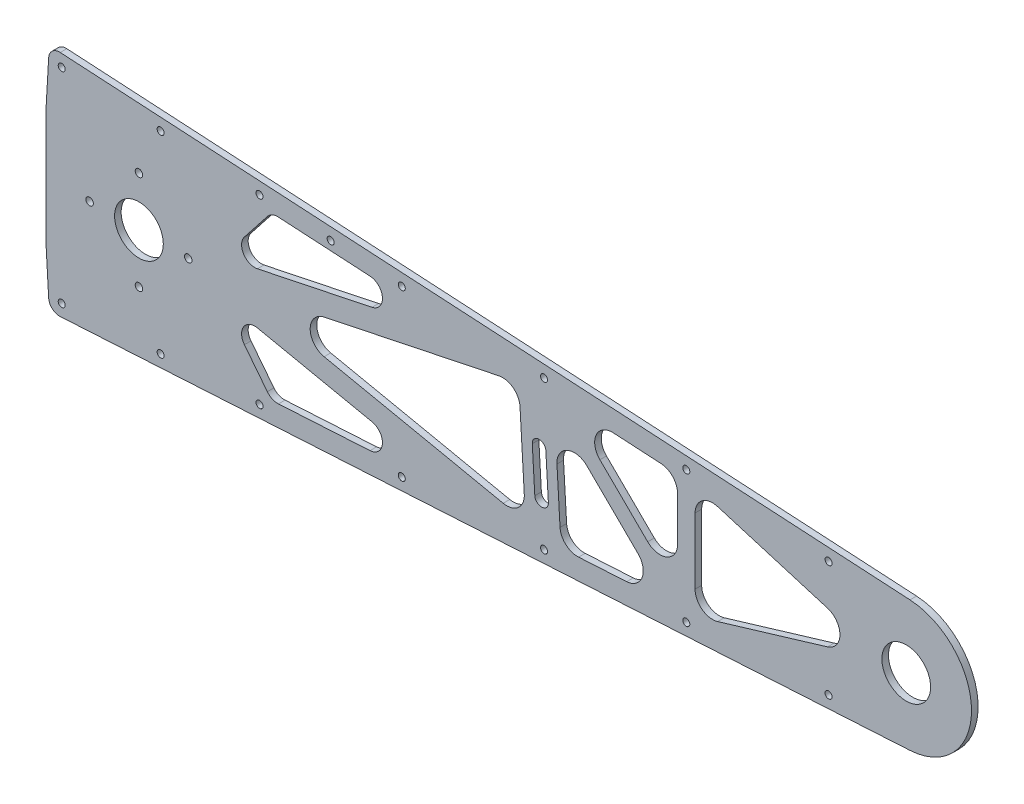
SolidWorks part; units mm, degrees
material "Thornel VCB-20 Carbon Cloth"
ref_plane "Front Plane" through (0, 0, 0) normal (0, 0, 1) x (1, 0, 0)
ref_plane "Top Plane" through (0, 0, 0) normal (0, 1, 0) x (1, 0, 0)
ref_plane "Right Plane" through (0, 0, 0) normal (1, 0, 0) x (0, 0, -1)
sketch "Sketch1" plane through (0, 0, 0) normal (0, 0, 1) x (1, 0, 0)
  line L0 (-175, 0) -> (175, 0) construction
  line L1 (-172.1122, 49.9165) -> (176.7203, 29.7354)
  line L2 (-172.1122, -49.9165) -> (176.7203, -29.7354)
  line L3 (139.566, 26.3757) -> (-120, 41.3925) construction
  line L4 (-55.1085, -37.6383) -> (9.783, -33.8841) construction
  line L5 (-125, 0) -> (-125, 62.9978) construction
  line L6 (-55.5713, 29.6383) -> (-120.4628, 33.3925) construction
  line L7 (-120.4628, 33.3925) -> (-120, 41.3925) construction
  line L8 (-55.5713, 29.6383) -> (-55.1085, 37.6383) construction
  line L9 (-88.0171, 31.5154) -> (-87.5543, 39.5154) construction
  line L10 (-120, -41.3925) -> (-165.1122, -44.0024) construction
  circle A0 centre (175, 0) radius 11.1125
  arc A1 (176.7203, 29.7354) -> (176.7203, -29.7354) centre (175, 0) cw
  circle A3 centre (-175, 0) radius 22.5 construction
  circle A7 centre (-175, 0) radius 11.1125
  circle A9 centre (-120, 41.3925) radius 1.6
  circle A10 centre (-55.1085, 37.6383) radius 1.6
  circle A11 centre (9.783, 33.8841) radius 1.6
  circle A12 centre (74.6745, 30.1299) radius 1.6
  circle A13 centre (139.566, 26.3757) radius 1.6
  circle A15 centre (139.566, -26.3757) radius 1.6
  circle A16 centre (74.6745, -30.1299) radius 1.6
  circle A17 centre (9.783, -33.8841) radius 1.6
  circle A18 centre (-55.1085, -37.6383) radius 1.6
  circle A19 centre (-120, -41.3925) radius 1.6
  arc A20 (-172.1122, 49.9165) -> (-172.1122, -49.9165) centre (-175, 0) ccw
  circle A21 centre (-87.5543, 39.5154) radius 1.6
  circle A22 centre (-165.1122, -44.0024) radius 1.6
  circle A23 centre (-165.1122, 44.0024) radius 1.6
  point P4 (0, 0)
  point P18 (-175, 22.5)
  point P21 (-197.5, 0)
  point P22 (-175, -22.5)
  point P23 (-152.5, 0)
  point P30 (-88.0171, 31.5154)
  dimension "D2" = 22.225
  dimension "D3" = 50
  dimension "D5" = 45
  dimension "D6" = 3.2
  dimension "D7" = 260
  dimension "D8" = 5
  dimension "D9" = 7
  dimension "D10" = 22.225
  dimension "D16" = 5
  dimension "D1" = 350
  dimension "D4" = 8
  dimension "D12" = 5.5
extrude "Boss-Extrude1" add sketch "Sketch1" along normal blind 3
sketch "Sketch4" plane through (0, 0, 3) normal (0, 0, 1) x (1, 0, 0)
  point P10 (-197.5, 0)
  point P13 (-175, 22.5)
  point P16 (-152.5, 0)
  point P19 (-175, -22.5)
hole_wizard "M3 Clearance Hole1" positions "Sketch4" profile "Sketch6" hole size "M3" standard "ANSI Metric" end condition up to next
sketch "Sketch6" plane through (-197.5, 0, 3) normal (1, 0, 0) x (0, -1, 0)
  line L0 (0, 0) -> (0, 3)
  line L1 (0, 3) -> (1.7, 3)
  line L2 (1.7, 3) -> (1.7, 0)
  line L5 (1.7, 0) -> (0, 0)
  line L11 (0, -6.35) -> (0, 107.95) construction
  dimension "Thru Hole Dia." = 3.4
  dimension "Thru Hole Depth" = 3
sketch "Sketch7" plane through (0, 0, 3) normal (0, 0, 1) x (1, 0, 0)
  line L0 (74.6745, 30.1299) -> (74.6745, -30.1299) construction
  line L1 (74.6745, -30.1299) -> (175, 0) construction
  line L2 (175, 0) -> (74.6745, 30.1299) construction
  line L3 (175, 0) -> (-152.5, 0) construction
  line L4 (175, -29.8349) -> (175, 29.8349) construction
  line L5 (88.9755, 22.7026) -> (139.0575, 7.6619)
  line L6 (139.0575, -7.6619) -> (88.9755, -22.7026)
  line L7 (78.6745, -15.0407) -> (78.6745, 15.0407)
  line L8 (9.783, -33.8841) -> (5.5294, 39.6394) construction
  line L9 (9.783, 33.8841) -> (74.6745, -30.1299) construction
  line L10 (9.783, 33.8841) -> (74.6745, 30.1299) construction
  line L11 (9.783, -33.8841) -> (74.6745, -30.1299) construction
  line L12 (-152.5, 0) -> (-55.1085, 37.6383) construction
  line L13 (-55.1085, 37.6383) -> (9.783, 33.8841) construction
  line L14 (9.783, 33.8841) -> (-152.5, 0) construction
  line L15 (70.6745, -1.436) -> (70.6745, 18.8041)
  line L16 (63.1365, 26.7907) -> (41.3408, 28.0517)
  line L17 (35.2605, 14.3698) -> (57.0563, -7.1312)
  line L18 (29.2743, 9.0376) -> (52.6422, -14.0143)
  line L19 (47.486, -27.6962) -> (25.5253, -28.9667)
  line L20 (17.0766, -21.4421) -> (15.6694, 2.8804)
  line L21 (176.7203, 29.7354) -> (-172.1122, 49.9165) construction
  line L22 (-172.1122, -49.9165) -> (176.7203, -29.7354) construction
  line L23 (0.7692, -16.5921) -> (-1.1805, 17.1091)
  line L24 (-10.8023, 24.4781) -> (-90.5308, 7.8311)
  line L25 (-90.5308, -7.8311) -> (-8.8525, -24.8852)
  line L35 (-197.5, 0) -> (-55.1085, 37.6383) construction
  line L52 (-55.1085, -37.6383) -> (-175, -22.5) construction
  line L53 (-15.2425, -47.7117) -> (-52.5586, -43) construction
  line L54 (-0.7058, -39.4678) -> (2.1851, -39.8329) construction
  line L55 (8.6627, -14.5198) -> (7.5076, 5.4468) construction
  line L56 (5.5679, -14.6989) -> (4.4127, 5.2678)
  line L57 (11.7575, -14.3408) -> (10.6024, 5.6258)
  line L58 (176.7203, 29.7354) -> (-172.1122, 49.9165) construction
  line L59 (-175, 22.5) -> (-165.1122, 44.0024) construction
  line L60 (-152.5, 0) -> (-120, 41.3925) construction
  line L61 (-126.8967, 21.2738) -> (-116.4321, 34.6016)
  line L62 (-111.3663, 36.8863) -> (-69.5778, 34.4687)
  line L63 (-68.698, 22.6054) -> (-120.9512, 11.6951)
  line L64 (-165.9126, 32.6875) -> (-164.3288, 36.1317)
  line L65 (-158.531, 39.6149) -> (-142.9867, 38.7156)
  line L66 (-138.6141, 29.0203) -> (-146.1029, 19.4825)
  line L67 (-175.7645, 30.4115) -> (-175.2558, 31.5179)
  line L68 (-197.5, 0) -> (-225, 0) construction
  line L69 (-208.0189, 4) -> (-206.9726, 4)
  line L70 (-208.0189, -4) -> (-206.9726, -4)
  line L71 (-175.7645, -30.4115) -> (-175.2558, -31.5179)
  line L72 (-165.9126, -32.6875) -> (-164.3288, -36.1317)
  line L73 (-158.531, -39.6149) -> (-142.9867, -38.7156)
  line L74 (-138.6141, -29.0203) -> (-146.1029, -19.4825)
  line L75 (-111.3663, -36.8863) -> (-69.5778, -34.4687)
  line L76 (-126.8967, -21.2738) -> (-116.4321, -34.6016)
  line L77 (-68.698, -22.6054) -> (-120.9512, -11.6951)
  arc A0 (139.0575, 7.6619) -> (139.0575, -7.6619) centre (136.7565, 0) cw
  arc A1 (88.9755, -22.7026) -> (78.6745, -15.0407) centre (86.6745, -15.0407) cw
  arc A2 (88.9755, 22.7026) -> (78.6745, 15.0407) centre (86.6745, 15.0407) ccw
  arc A3 (70.6745, 18.8041) -> (63.1365, 26.7907) centre (62.6745, 18.8041) ccw
  arc A4 (41.3408, 28.0517) -> (35.2605, 14.3698) centre (40.8787, 20.065) ccw
  arc A5 (70.6745, -1.436) -> (57.0563, -7.1312) centre (62.6745, -1.436) cw
  arc A6 (52.6422, -14.0143) -> (47.486, -27.6962) centre (47.024, -19.7095) cw
  arc A7 (25.5253, -28.9667) -> (17.0766, -21.4421) centre (25.0632, -20.98) cw
  arc A8 (29.2743, 9.0376) -> (15.6694, 2.8804) centre (23.6561, 3.3424) ccw
  arc A9 (0.7692, -16.5921) -> (-8.8525, -24.8852) centre (-7.2174, -17.0541) cw
  arc A10 (-1.1805, 17.1091) -> (-10.8023, 24.4781) centre (-9.1672, 16.647) ccw
  arc A11 (-90.5308, 7.8311) -> (-90.5308, -7.8311) centre (-88.8957, 0) ccw
  circle A30 centre (-175, 0) radius 11.1125 construction
  circle A31 centre (-175, 0) radius 11.1125 construction
  circle A32 centre (-175, 0) radius 22.5 construction
  circle A49 centre (9.783, -33.8841) radius 1.6 construction
  circle A50 centre (9.783, -33.8841) radius 1.6
  circle A52 centre (175, 0) radius 11.1125 construction
  circle A53 centre (175, 0) radius 11.1125 construction
  arc A56 (5.5679, -14.6989) -> (11.7575, -14.3408) centre (8.6627, -14.5198) ccw
  arc A57 (10.6024, 5.6258) -> (4.4127, 5.2678) centre (7.5076, 5.4468) ccw
  circle A58 centre (-165.1122, 44.0024) radius 1.6 construction
  circle A60 centre (-120, 41.3925) radius 1.6 construction
  arc A61 (-155.1524, 19.0348) -> (-163.0653, 24.7753) centre (-175, 0) ccw
  arc A62 (-180.1025, 27.0225) -> (-201.2462, 8.209) centre (-175, 0) ccw
  arc A63 (-181.6995, 39.942) -> (-213.7614, 11.7391) centre (-175, 0) ccw
  arc A64 (-172.1122, 49.9165) -> (-172.1122, -49.9165) centre (-175, 0) ccw construction
  arc A65 (-175.2558, 31.5179) -> (-181.6995, 39.942) centre (-180.707, 34.0247) ccw
  arc A66 (-213.7614, 11.7391) -> (-208.0189, 4) centre (-208.0189, 10) ccw
  arc A67 (-201.2462, 8.209) -> (-206.9726, 4) centre (-206.9726, 10) cw
  arc A68 (-180.1025, 27.0225) -> (-175.7645, 30.4115) centre (-181.2158, 32.9183) ccw
  arc A69 (-69.5778, 34.4687) -> (-68.698, 22.6054) centre (-69.9244, 28.4787) cw
  arc A70 (-116.4321, 34.6016) -> (-111.3663, 36.8863) centre (-111.7129, 30.8963) cw
  arc A71 (-126.8967, 21.2738) -> (-120.9512, 11.6951) centre (-122.1775, 17.5685) ccw
  arc A72 (-142.9867, 38.7156) -> (-138.6141, 29.0203) centre (-143.3332, 32.7257) cw
  arc A73 (-164.3288, 36.1317) -> (-158.531, 39.6149) centre (-158.8776, 33.625) cw
  arc A74 (-163.0653, 24.7753) -> (-165.9126, 32.6875) centre (-160.4614, 30.1808) cw
  arc A75 (-155.1524, 19.0348) -> (-146.1029, 19.4825) centre (-150.822, 23.1878) ccw
  arc A76 (-213.7614, -11.7391) -> (-208.0189, -4) centre (-208.0189, -10) cw
  arc A77 (-201.2462, -8.209) -> (-206.9726, -4) centre (-206.9726, -10) ccw
  arc A78 (-180.1025, -27.0225) -> (-201.2462, -8.209) centre (-175, 0) cw
  arc A79 (-181.6995, -39.942) -> (-213.7614, -11.7391) centre (-175, 0) cw
  arc A80 (-180.1025, -27.0225) -> (-175.7645, -30.4115) centre (-181.2158, -32.9183) cw
  arc A81 (-175.2558, -31.5179) -> (-181.6995, -39.942) centre (-180.707, -34.0247) cw
  arc A82 (-164.3288, -36.1317) -> (-158.531, -39.6149) centre (-158.8776, -33.625) ccw
  arc A83 (-163.0653, -24.7753) -> (-165.9126, -32.6875) centre (-160.4614, -30.1808) ccw
  arc A84 (-155.1524, -19.0348) -> (-163.0653, -24.7753) centre (-175, 0) cw
  arc A85 (-155.1524, -19.0348) -> (-146.1029, -19.4825) centre (-150.822, -23.1878) cw
  arc A86 (-142.9867, -38.7156) -> (-138.6141, -29.0203) centre (-143.3332, -32.7257) ccw
  arc A87 (-69.5778, -34.4687) -> (-68.698, -22.6054) centre (-69.9244, -28.4787) ccw
  arc A88 (-116.4321, -34.6016) -> (-111.3663, -36.8863) centre (-111.7129, -30.8963) ccw
  arc A89 (-126.8967, -21.2738) -> (-120.9512, -11.6951) centre (-122.1775, -17.5685) cw
  point P36 (164.5699, 0)
  point P59 (-128.0368, 0)
  point P102 (-15.2425, -47.7117)
  point P126 (8.0851, -4.5365)
  dimension "D8" = 8
  dimension "D11" = 27.5
  dimension "D12" = 5
  dimension "D20" = 3.1
  dimension "D10" = 7
  dimension "D17" = 6
  dimension "D1" = 3
  dimension "D3" = 8
  dimension "D4" = 8
  dimension "D5" = 8
  dimension "D6" = 16
  dimension "D7" = 10
  dimension "D9" = 8
  dimension "D13" = 8
  dimension "D14" = 5
  dimension "D15" = 8
  dimension "D16" = 24.8967
  dimension "D22" = 20
extrude "Cut-Extrude1" cut sketch "Sketch7" against normal blind 10 contours L57 A57 L56 A56 | L24 A11 L25 A9 L23 A10 | L18 A8 L20 A7 L19 A6 | A89 L76 A88 L75 A87 L77 | L61 A71 L63 A69 L62 A70 | L20 A8 L18 A6 L19 A7 | L17 A5 L15 A3 L16 A4 | L7 A2 L5 A0 L6 A1 | L75 A87 L77 A89 L76 A88 region at (32.1755, -11.823, 3) region at (-38.9372, -0.1884, 3) region at (8.0851, -4.5365, 3) region at (-98.2756, 25.5667, 3) region at (-98.2756, -25.5667, 3)
sketch "Sketch9" [suppressed] plane through (0, 0, 3) normal (0, 0, 1) x (1, 0, 0)
  line L2 (176.7203, 29.7354) -> (-172.1122, 49.9165) construction
  line L3 (-172.1122, -49.9165) -> (176.7203, -29.7354) construction
  line L4 (254.5375, 0) -> (208, 0) construction
  line L5 (200.557, 2) -> (203.931, 2)
  line L6 (200.557, -2) -> (203.931, -2)
  line L7 (162.9445, 26.3755) -> (155.7345, 26.7926)
  line L8 (162.9445, -26.3755) -> (155.7345, -26.7926)
  arc A1 (155.7345, -26.7926) -> (155.7345, 26.7926) centre (175, 0) ccw
  arc A2 (176.7203, -29.7354) -> (176.7203, 29.7354) centre (175, 0) ccw construction
  arc A3 (200.557, -2) -> (200.557, 2) centre (175, 0) ccw
  arc A4 (162.9445, 26.3755) -> (203.931, 2) centre (175, 0) cw
  arc A5 (203.931, -2) -> (162.9445, -26.3755) centre (175, 0) cw
  dimension "D1" = 33
  dimension "D2" = 4
  dimension "D3" = 4
extrude "Boss-Extrude2" [suppressed] add sketch "Sketch9" against normal up to surface (3 mm away) up to face at (-102.0595, -26.743, 0)
fillet "Fillet1" [suppressed] radius 1
fillet "Fillet2" [suppressed] radius 80
sketch "Sketch10" plane through (0, 0, 3) normal (0, 0, 1) x (1, 0, 0)
  line L0 (-165.1122, 44.0024) -> (-120, 41.3925) construction
  line L1 (-165.1122, 44.0024) -> (-210.2243, 46.6123) construction
  line L2 (-172.1122, 49.9165) -> (-210.905, 52.1608)
  line L3 (176.7203, 29.7354) -> (-172.1122, 49.9165) construction
  line L4 (-216.1854, 47.458) -> (-217.3977, 26.5035)
  line L5 (-172.1122, 49.9165) -> (-217.3977, 26.5035)
  circle A0 centre (-120, 41.3925) radius 1.6 construction
  circle A1 centre (-165.1122, 44.0024) radius 1.6 construction
  circle A2 centre (-210.2243, 46.6123) radius 1.6
  arc A3 (-172.1122, 49.9165) -> (-172.1122, -49.9165) centre (-175, 0) ccw construction
  arc A4 (-210.905, 52.1608) -> (-216.1854, 47.458) centre (-211.1938, 47.1692) ccw
  dimension "D2" = 5
  dimension "D1" = 6
extrude "Boss-Extrude3" add sketch "Sketch10" against normal up to surface (3 mm away) up to face at (-102.0595, -26.743, 0)
mirror "Mirror1" about plane through (0, 0, 0) normal (0, 1, 0) of "Boss-Extrude3"
sketch "Sketch11" plane through (0, 0, 0) normal (0, 0, -1) x (-1, 0, 0)
  line L0 (217.3977, -26.5035) -> (217.3977, 26.5035)
  arc A0 (217.3977, -26.5035) -> (217.3977, 26.5035) centre (175, 0) ccw construction
  arc A1 (217.3977, -26.5035) -> (217.3977, 26.5035) centre (175, 0) ccw
extrude "Cut-Extrude2" cut sketch "Sketch11" against normal through all both and the other way through all
